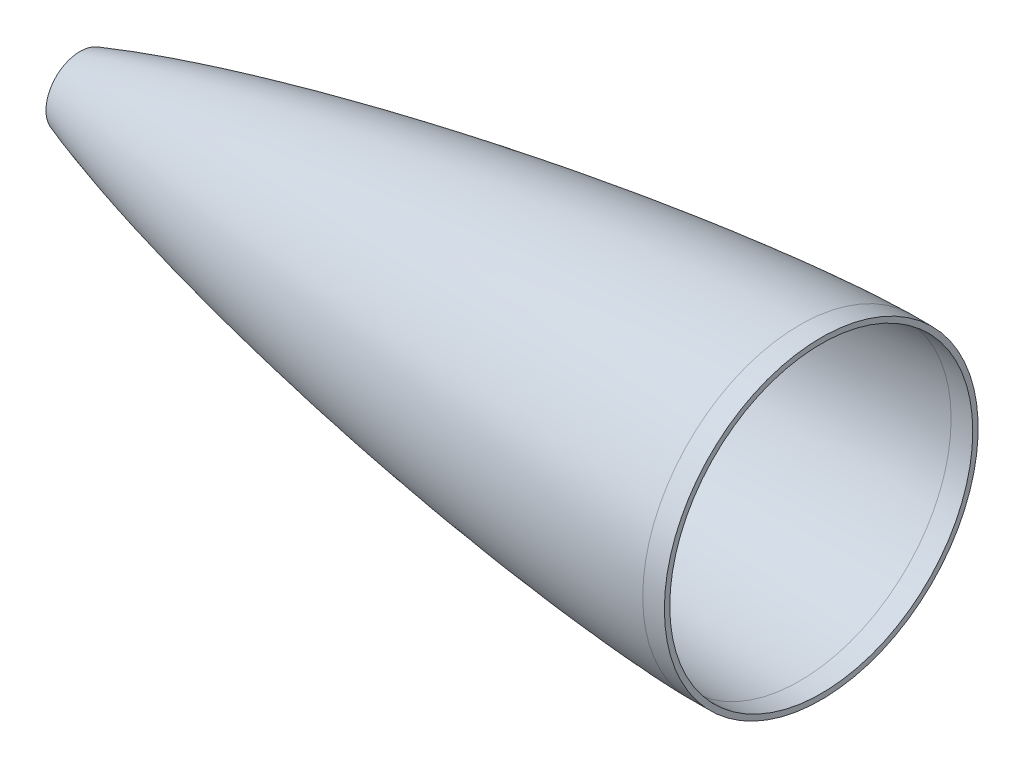
SolidWorks part; units mm, degrees
ref_plane "Front Plane" through (0, 0, 0) normal (0, 0, 1) x (1, 0, 0)
ref_plane "Top Plane" through (0, 0, 0) normal (0, 1, 0) x (1, 0, 0)
ref_plane "Right Plane" through (0, 0, 0) normal (1, 0, 0) x (0, 0, -1)
sketch "Sketch1" plane through (0, 0, 0) normal (0, 0, 1) x (1, 0, 0)
  line L0 (0, 0) -> (457.2, 0) construction
  line L2 (457.2, 88.9151) -> (457.2, 0) construction
  line L5 (457.2, 0) -> (469.893, 0)
  line L7 (457.2, 88.9151) -> (469.893, 88.9151)
  line L8 (469.893, 0) -> (469.893, 88.9151) construction
  line L12 (457.193, 92.0901) -> (473.068, 92.0901) construction
  line L13 (457.193, 92.0901) -> (469.893, 92.0901)
  line L14 (469.893, 92.0901) -> (469.893, 88.9151)
  line L15 (457.2, 0) -> (-3.2335, 0) construction
  line L16 (473.068, -3.175) -> (473.068, 92.0901) construction
  line L17 (457.2, 0) -> (0, 0) construction
  line L18 (457.2, -3.175) -> (-3.8458, -3.175) construction
  line L19 (457.2, -3.175) -> (473.068, -3.175) construction
  line L20 (-3.2335, 0) -> (0, 0)
  spline S0 degree 4 poles (0, 0) (0.0023, 0.0117) (0.0082, 0.0346) (0.0259, 0.0787) (0.0695, 0.163) (0.1339, 0.2631) (0.2191, 0.3779) (0.3369, 0.5207) (0.5082, 0.71) (0.7967, 0.9964) (1.2973, 1.4371) (2.1712, 2.1158) (3.7004, 3.1565) (6.4155, 4.7689) (11.1356, 7.1992) (18.8819, 10.6607) (32.1609, 15.8309) (51.2281, 22.2453) (75.2291, 29.3426) (102.987, 36.6637) (131.6184, 43.5191) (160.3731, 49.8355) (189.2264, 55.6835) (218.1627, 61.1047) (247.1713, 66.1244) (276.2447, 70.7536) (305.3776, 74.9923) (334.5665, 78.8281) (363.8087, 82.2339) (389.4414, 84.7941) (411.4449, 86.6328) (428.6333, 87.7894) (439.7384, 88.3858) (448.4262, 88.7338) (453.4393, 88.8671) (455.9463, 88.9096) (457.2, 88.9151) knots 0 0 0 0 0 0.000101 0.000202 0.000405 0.000809 0.001116 0.001422 0.001985 0.002988 0.004584 0.007113 0.011426 0.01877 0.031526 0.052412 0.083828 0.140383 0.203215 0.266046 0.328877 0.391708 0.454539 0.51737 0.580202 0.643033 0.705864 0.768695 0.831526 0.894357 0.925773 0.957189 0.978594 0.989297 1 1 1 1 1 construction
  spline S1 degree 4 poles (0, 0) (0.0023, 0.0117) (0.0082, 0.0346) (0.0259, 0.0787) (0.0695, 0.163) (0.1339, 0.2631) (0.2191, 0.3779) (0.3369, 0.5207) (0.5082, 0.71) (0.7967, 0.9964) (1.2973, 1.4371) (2.1712, 2.1158) (3.7004, 3.1565) (6.4155, 4.7689) (11.1356, 7.1992) (18.8819, 10.6607) (32.1609, 15.8309) (51.2281, 22.2453) (75.2291, 29.3426) (102.987, 36.6637) (131.6184, 43.5191) (160.3731, 49.8355) (189.2264, 55.6835) (218.1627, 61.1047) (247.1713, 66.1244) (276.2447, 70.7536) (305.3776, 74.9923) (334.5665, 78.8281) (363.8087, 82.2339) (389.4414, 84.7941) (411.4449, 86.6328) (428.6333, 87.7894) (439.7384, 88.3858) (448.4262, 88.7338) (453.4393, 88.8671) (455.9463, 88.9096) (457.2, 88.9151) knots 0 0 0 0 0 0.000101 0.000202 0.000405 0.000809 0.001116 0.001422 0.001985 0.002988 0.004584 0.007113 0.011426 0.01877 0.031526 0.052412 0.083828 0.140383 0.203215 0.266046 0.328877 0.391708 0.454539 0.51737 0.580202 0.643033 0.705864 0.768695 0.831526 0.894357 0.925773 0.957189 0.978594 0.989297 1 1 1 1 1
  spline S2 degree 1 poles (-3.8458, -3.175) (457.193, 92.0901) knots 0 0 1 1 construction
  spline S3 degree 3 poles (-3.8458, -3.175) (-3.7874, -2.872) (-3.6998, -2.4175) (-3.5829, -1.8115) (-3.4952, -1.357) (-3.4076, -0.9025) (-3.3345, -0.5238) (-3.2761, -0.2208) (-3.2396, -0.0314) (-3.2103, 0.1201) (-3.1884, 0.2337) (-3.1702, 0.3285) (-3.1556, 0.4041) (-3.1445, 0.4613) (-3.1357, 0.5073) (-3.1278, 0.548) (-3.1248, 0.5645) (-3.1179, 0.5981) (-3.1239, 0.5726) (-3.0922, 0.7239) (-3.0624, 0.8441) (-3, 1.0595) (-2.9104, 1.2902) (-2.8398, 1.4448) (-2.7785, 1.5681) (-2.703, 1.7084) (-2.6203, 1.8485) (-2.528, 1.9923) (-2.3595, 2.2367) (-2.143, 2.509) (-1.8818, 2.8025) (-1.6376, 3.0537) (-1.3243, 3.3555) (-0.9486, 3.6887) (-0.5103, 4.0488) (0.0661, 4.4942) (0.7754, 5.0026) (1.6225, 5.5673) (2.4659, 6.098) (3.3104, 6.6047) (4.4371, 7.2534) (5.8471, 8.023) (7.5464, 8.9) (9.2508, 9.7388) (11.5294, 10.8167) (14.3919, 12.1013) (17.8436, 13.5648) (22.4643, 15.4343) (28.2723, 17.6439) (35.2778, 20.1452) (42.3149, 22.5272) (51.7314, 25.5685) (63.5532, 29.1598) (77.804, 33.2079) (92.1054, 37.0393) (106.4493, 40.6858) (120.8289, 44.1698) (140.0439, 48.6197) (164.1321, 53.8477) (193.1291, 59.6555) (222.2046, 65.0369) (251.3498, 70.0155) (280.5589, 74.6011) (309.8282, 78.7918) (339.1555, 82.573) (368.5408, 85.9137) (393.079, 88.285) (412.7434, 89.8798) (427.5132, 90.8996) (439.8369, 91.57) (448.4928, 91.9054) (453.4377, 92.041) (455.9439, 92.0846) (457.193, 92.0901) knots -0.00818 -0.00818 -0.00818 -0.00818 -0.006211 -0.005227 -0.004242 -0.003258 -0.002273 -0.001781 -0.001288 -0.001042 -0.000796 -0.00055 -0.000427 -0.000304 -0.000181 -0.000119 -0.000058 -0.000027 0.000004 0.000019 0.000035 0.000065 0.000127 0.000188 0.00025 0.000311 0.000435 0.000558 0.000681 0.001173 0.001665 0.002158 0.00265 0.003634 0.004619 0.005604 0.007573 0.009542 0.011511 0.01348 0.015449 0.019387 0.023326 0.027264 0.031202 0.039079 0.046955 0.054832 0.070585 0.086338 0.102091 0.117844 0.14935 0.180856 0.212362 0.243868 0.275375 0.306881 0.369893 0.432905 0.495917 0.558929 0.621942 0.684954 0.747966 0.810978 0.873991 0.905497 0.937003 0.968509 0.984262 0.992138 1.000015 1.000015 1.000015 1.000015 only from (-3.2335, 0) to (457.193, 92.0901)
  dimension "D1" = 457.2
  dimension "D3" = 12.7
  dimension "D4" = 3.175
revolve "Revolve3" add sketch "Sketch1" angle 360 about L0
ref_plane "Plane1" through (-3.2335, 0, 0) normal (1, 0, 0) x (0, 0, -1)
sketch "Sketch2" plane through (-3.2335, 0, 0) normal (1, 0, 0) x (0, 0, -1)
  circle A0 centre (0, 0) radius 92.0901 construction
  circle A1 centre (0, 0) radius 92.0901
extrude "Cut-Extrude1" cut sketch "Sketch2" along normal blind 38.1
